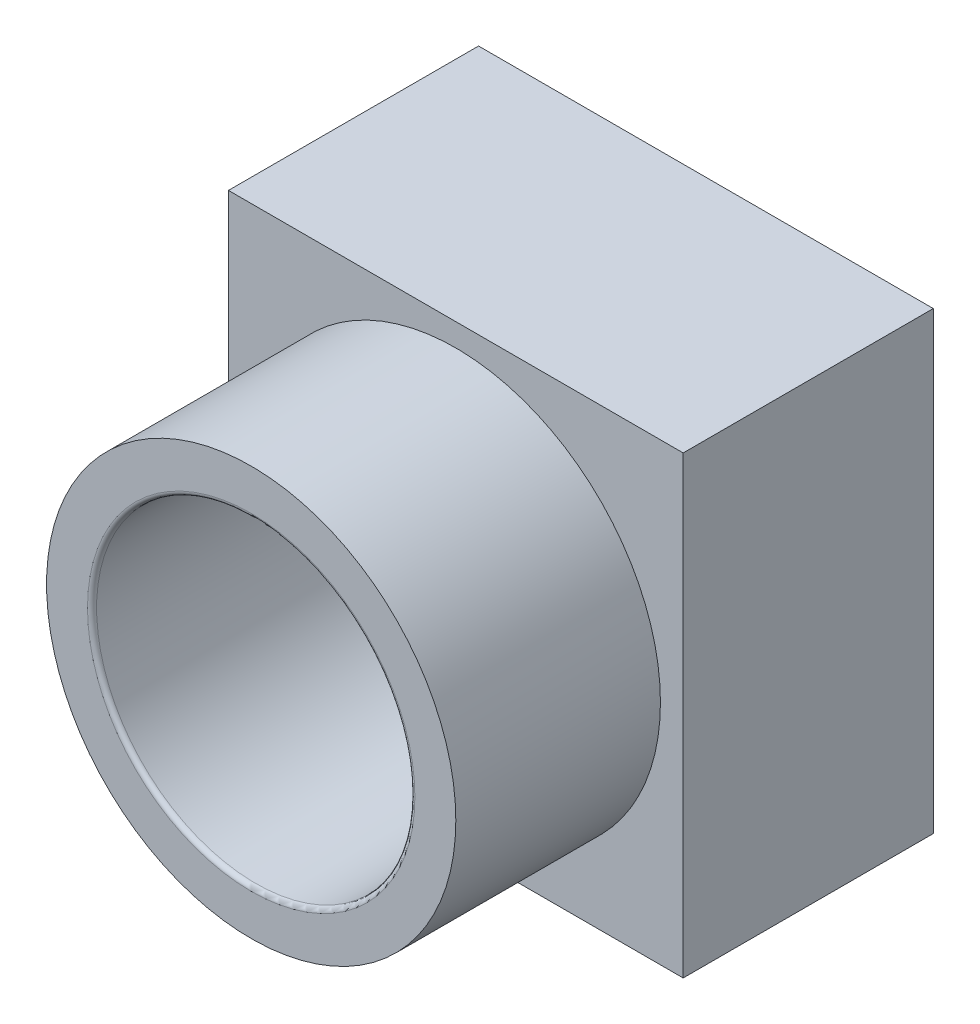
SolidWorks part; units mm, degrees
ref_plane "Front Plane" through (0, 0, 0) normal (0, 0, 1) x (1, 0, 0)
ref_plane "Top Plane" through (0, 0, 0) normal (0, 1, 0) x (1, 0, 0)
ref_plane "Right Plane" through (0, 0, 0) normal (1, 0, 0) x (0, 0, -1)
sketch "Sketch1" plane through (0, 0, 0) normal (0, 0, 1) x (1, 0, 0)
  line L1 (-12.7, 12.7) -> (12.7, 12.7)
  line L2 (-12.7, 12.7) -> (-12.7, -12.7)
  line L3 (-12.7, -12.7) -> (12.7, -12.7)
  line L4 (12.7, 12.7) -> (12.7, -12.7)
  line L5 (-12.7, 12.7) -> (12.7, -12.7) construction
  point P4 (14.5393, -12.7)
  dimension "D1" = 25.4
  dimension "D2" = 25.4
extrude "Boss-Extrude1" add sketch "Sketch1" against normal blind 25.4
ref_plane "Plane1" through (0, 0, -13.97) normal (0, 0, 1) x (1, 0, 0)
sketch "Sketch2" plane through (0, 0, -13.97) normal (0, 0, 1) x (1, 0, 0)
  line L0 (-10.16, -10.16) -> (10.16, -10.16)
  line L1 (10.16, -10.16) -> (10.16, 10.16)
  line L2 (10.16, 10.16) -> (-10.16, 10.16)
  line L3 (-10.16, 10.16) -> (-10.16, -10.16)
  line L4 (-12.7, 12.7) -> (-12.7, -12.7)
  line L5 (12.7, 12.7) -> (-12.7, 12.7)
  line L6 (12.7, -12.7) -> (12.7, 12.7)
  line L7 (-12.7, -12.7) -> (12.7, -12.7)
  line L8 (-12.7, 12.7) -> (-12.7, -12.7) construction
  line L9 (12.7, 12.7) -> (-12.7, 12.7) construction
  line L10 (12.7, -12.7) -> (12.7, 12.7) construction
  line L11 (-12.7, -12.7) -> (12.7, -12.7) construction
  dimension "D1" = 0
  dimension "D2" = 2.54
extrude "Cut-Extrude1" cut sketch "Sketch2" against normal through all
sketch "Sketch3" plane through (0, 0, 0) normal (0, 0, 1) x (1, 0, 0)
  circle A0 centre (0, 0) radius 8.89
  dimension "D1" = 17.78
extrude "Cut-Extrude2" cut sketch "Sketch3" against normal through all both and the other way through all
ref_plane "Plane2" through (0, 0, -11.43) normal (0, 0, 1) x (1, 0, 0)
sketch "Sketch4" plane through (0, 0, -11.43) normal (0, 0, 1) x (1, 0, 0)
  circle A0 centre (0, 0) radius 8.89 construction
  circle A1 centre (0, 0) radius 8.89 construction
  circle A2 centre (0, 0) radius 11.43
  circle A3 centre (0, 0) radius 63.5
  dimension "D2" = 127
  dimension "D1" = 2.54
extrude "Cut-Extrude3" cut sketch "Sketch4" along normal through all
fillet "Fillet1" radius 1.27 4 edges at (0, -10.16, -13.97) (10.16, 0, -13.97) (0, 10.16, -13.97) (-10.16, 0, -13.97)
fillet "Fillet2" radius 1.27 8 edges at (-9.788, -9.788, -14.342) (-9.788, 9.788, -14.342) (9.788, 9.788, -14.342) (9.788, -9.788, -14.342) (-10.16, -10.16, -20.32) (-10.16, 10.16, -20.32) (10.16, 10.16, -20.32) (10.16, -10.16, -20.32)
fillet "Fillet3" radius 0.254 5 edges at (-6.2862, 6.2862, -13.97) (-6.2862, -6.2862, -13.97) (6.2862, -6.2862, -13.97) (6.2862, 6.2862, -13.97) (8.89, 0, 0)
